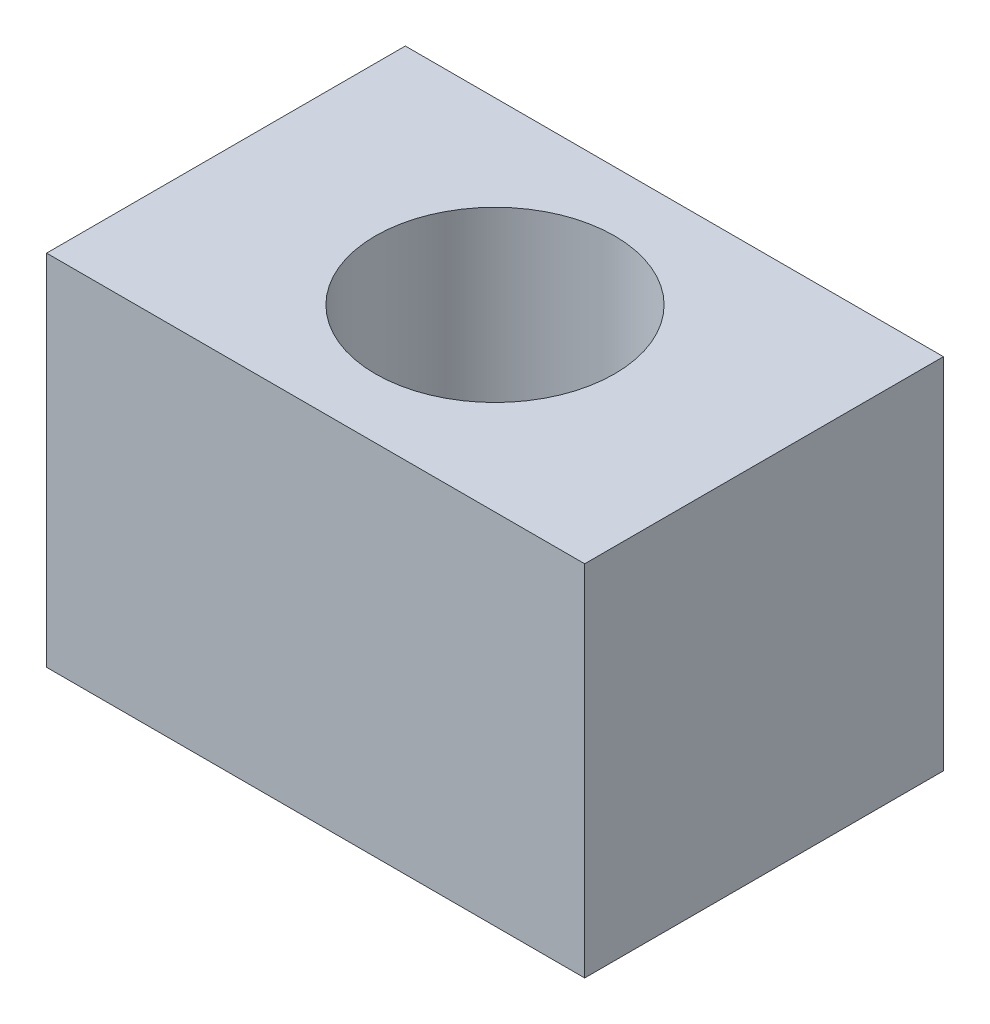
SolidWorks part; units mm, degrees
ref_plane "Plan de face" through (0, 0, 0) normal (0, 0, 1) x (1, 0, 0)
ref_plane "Plan de dessus" through (0, 0, 0) normal (0, 1, 0) x (1, 0, 0)
ref_plane "Plan de droite" through (0, 0, 0) normal (1, 0, 0) x (0, 0, -1)
sketch "Esquisse1" plane through (0, 0, 0) normal (0, 1, 0) x (1, 0, 0)
  line L1 (-4.5, -3) -> (4.5, -3)
  line L2 (-4.5, -3) -> (-4.5, 3)
  line L3 (-4.5, 3) -> (4.5, 3)
  line L4 (4.5, -3) -> (4.5, 3)
  line L5 (-4.5, -3) -> (4.5, 3) construction
  line L6 (-4.5, 3) -> (4.5, -3) construction
  circle A0 centre (0, 0) radius 2
  point P0 (0, 0)
  dimension "D3" = 4
  dimension "D1" = 9
  dimension "D2" = 6
extrude "Boss.-Extru.1" add sketch "Esquisse1" along normal blind 6
